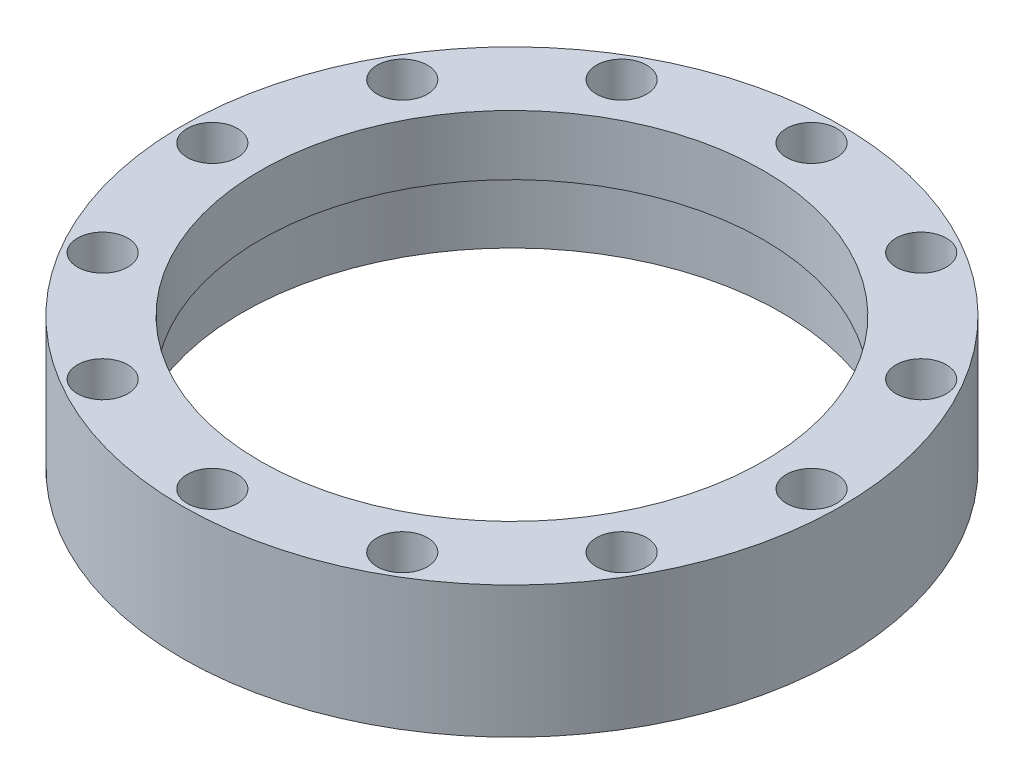
SolidWorks part; units mm, degrees
ref_plane "Front Plane" through (0, 0, 0) normal (0, 0, 1) x (1, 0, 0)
ref_plane "Top Plane" through (0, 0, 0) normal (0, 1, 0) x (1, 0, 0)
ref_plane "Right Plane" through (0, 0, 0) normal (1, 0, 0) x (0, 0, -1)
sketch "Sketch1" plane through (0, 0, 0) normal (0, 1, 0) x (1, 0, 0)
  line L0 (0, 45.5757) -> (0, -41.4521) construction
  circle A0 centre (0, 0) radius 27.5
  circle A1 centre (0, 0) radius 25 construction
  circle A2 centre (0, 0) radius 22.5
  circle A3 centre (0, 25) radius 1.5
  circle A4 centre (12.5, 21.6506) radius 1.5
  circle A5 centre (21.6506, 12.5) radius 1.5
  circle A6 centre (25, 0) radius 1.5
  circle A7 centre (21.6506, -12.5) radius 1.5
  circle A8 centre (12.5, -21.6506) radius 1.5
  circle A9 centre (0, -25) radius 1.5
  circle A10 centre (-12.5, -21.6506) radius 1.5
  circle A11 centre (-21.6506, -12.5) radius 1.5
  circle A12 centre (-25, 0) radius 1.5
  circle A13 centre (-21.6506, 12.5) radius 1.5
  circle A14 centre (-12.5, 21.6506) radius 1.5
  point P31 (0, 0)
  point P32 (0, 25)
  dimension "D1" = 55
  dimension "D2" = 50
  dimension "D3" = 45
  dimension "D4" = 3
  dimension "D5" = 12
extrude "Boss-Extrude1" add sketch "Sketch1" along normal blind 11
sketch "Sketch2" plane through (0, 11, 0) normal (0, 1, 0) x (1, 0, 0)
  circle A0 centre (0, 0) radius 22.5
  circle A1 centre (0, 0) radius 21
  dimension "D1" = 42
extrude "Boss-Extrude2" add sketch "Sketch2" against normal blind 5
sketch "Sketch3" plane through (0, 11, 0) normal (0, 1, 0) x (1, 0, 0)
  circle A0 centre (0, 25) radius 2.1
  circle A1 centre (12.5, 21.6506) radius 2.1
  circle A2 centre (21.6506, 12.5) radius 2.1
  circle A3 centre (25, 0) radius 2.1
  circle A4 centre (21.6506, -12.5) radius 2.1
  circle A5 centre (12.5, -21.6506) radius 2.1
  circle A6 centre (0, -25) radius 2.1
  circle A7 centre (-12.5, -21.6506) radius 2.1
  circle A8 centre (-21.6506, -12.5) radius 2.1
  circle A9 centre (-25, 0) radius 2.1
  circle A10 centre (-21.6506, 12.5) radius 2.1
  circle A11 centre (-12.5, 21.6506) radius 2.1
  point P28 (0, 0)
  dimension "D2" = 4.2
  dimension "D1" = 12
extrude "Cut-Extrude1" cut sketch "Sketch3" against normal blind 5
